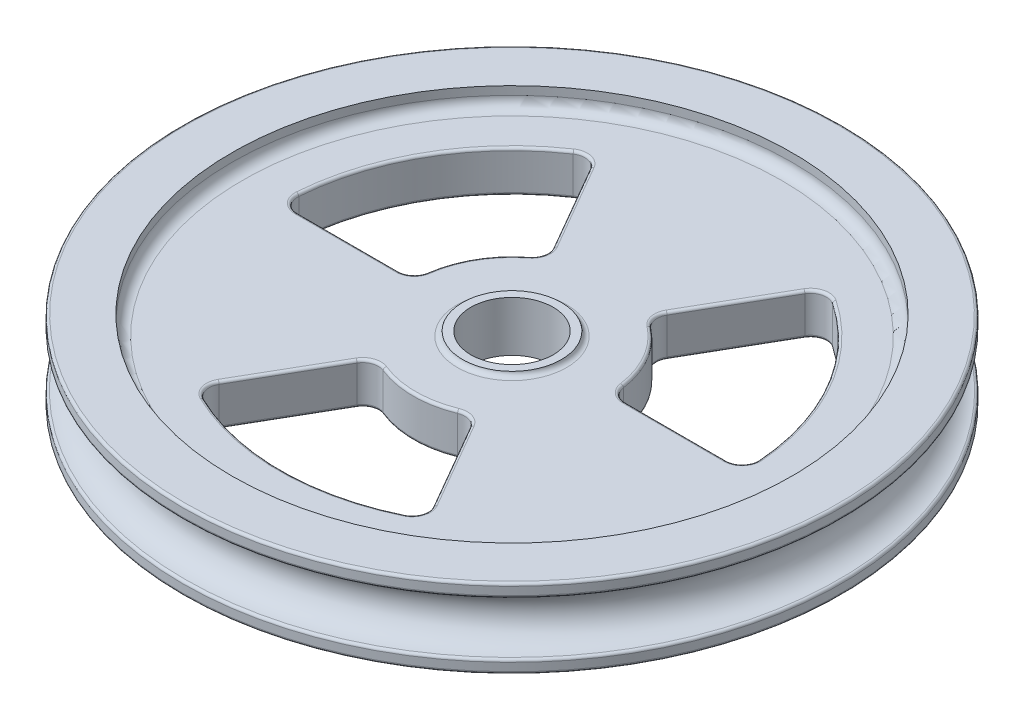
SolidWorks part; units mm, degrees
ref_plane "Front Plane" through (0, 0, 0) normal (0, 0, 1) x (1, 0, 0)
ref_plane "Top Plane" through (0, 0, 0) normal (0, 1, 0) x (1, 0, 0)
ref_plane "Right Plane" through (0, 0, 0) normal (1, 0, 0) x (0, 0, -1)
sketch "Sketch1" plane through (0, 0, 0) normal (0, 0, 1) x (1, 0, 0)
  line L0 (100, 12) -> (0, 12)
  line L1 (0, 12) -> (0, -12)
  line L2 (0, -12) -> (100, -12)
  line L3 (100, -12) -> (100, -8)
  line L4 (100, 8) -> (100, 12)
  line L5 (0, 12) -> (0, -12) construction
  arc A0 (100, -8) -> (100, 8) centre (100, 0) cw
  dimension "D1" = 100
revolve "Revolve1" add sketch "Sketch1" angle 360 about L5 reverse direction yes
hole_wizard "Hole1" positions "Sketch3" profile "Sketch2" legacy
sketch "Sketch3" plane through (0, -12, 0) normal (0, -1, 0) x (-1, 0, 0)
  point P0 (0, 0)
sketch "Sketch2" plane through (0, -12, 0) normal (1, 0, 0) x (0, 0, -1)
  line L0 (0, 0) -> (0, 5.715)
  line L1 (0, 5.715) -> (85, 5.715)
  line L2 (85, 5.715) -> (85, 0)
  line L3 (85, 0) -> (0, 0)
  line L4 (0, 110) -> (0, -10) construction
  dimension "Diameter" = 170
  dimension "Depth" = 5.715
hole_wizard "Hole2" positions "Sketch5" profile "Sketch4" legacy
sketch "Sketch5" plane through (0, 12, 0) normal (0, 1, 0) x (1, 0, 0)
  point P0 (0, 0)
sketch "Sketch4" plane through (0, 12, 0) normal (1, 0, 0) x (0, 0, 1)
  line L0 (0, 0) -> (0, 5.715)
  line L1 (0, 5.715) -> (85, 5.715)
  line L2 (85, 5.715) -> (85, 0)
  line L3 (85, 0) -> (0, 0)
  line L4 (0, 110) -> (0, -10) construction
  dimension "Diameter" = 170
  dimension "Depth" = 5.715
sketch "Sketch6" plane through (0, -6.285, 0) normal (0, -1, 0) x (1, 0, 0)
  line L0 (-35, -60.6218) -> (-15, -25.9808)
  line L1 (-30, 0) -> (-70, 0)
  arc A0 (-70, 0) -> (-35, -60.6218) centre (0, 0) ccw
  arc A1 (-15, -25.9808) -> (-30, 0) centre (0, 0) cw
  point P5 (0, 0)
  dimension "D3" = 70
  dimension "D1" = 30
extrude "Cut-Extrude1" cut sketch "Sketch6" against normal through all
sketch "Sketch7" plane through (0, -6.285, 0) normal (0, -1, 0) x (1, 0, 0)
  line L0 (-35, 60.6218) -> (-15, 25.9808)
  line L1 (15, 25.9808) -> (35, 60.6218)
  arc A0 (35, 60.6218) -> (-35, 60.6218) centre (0, 0) ccw
  arc A1 (-15, 25.9808) -> (15, 25.9808) centre (0, 0) cw
  point P5 (0, 0)
  dimension "D1" = 30
  dimension "D2" = 70
extrude "Cut-Extrude2" cut sketch "Sketch7" against normal through all
sketch "Sketch8" plane through (0, 6.285, 0) normal (0, 1, 0) x (-1, 0, 0)
  line L0 (-35, -60.6218) -> (-15, -25.9808)
  line L1 (-30, 0) -> (-70, 0)
  arc A0 (-15, -25.9808) -> (-30, 0) centre (0, 0) cw
  arc A1 (-70, 0) -> (-35, -60.6218) centre (0, 0) ccw
  point P5 (0, 0)
  dimension "D1" = 30
  dimension "D2" = 70
extrude "Cut-Extrude3" cut sketch "Sketch8" against normal through all
sketch "Sketch9" plane through (0, 0, 0) normal (0, 0, 1) x (1, 0, 0)
  line L0 (15, 7.62) -> (0, 7.62)
  line L1 (0, 7.62) -> (0, 1.905)
  line L2 (0, 1.905) -> (15, 1.905)
  line L3 (15, 1.905) -> (15, 7.62)
  line L4 (0, 7.62) -> (0, 1.905) construction
  dimension "D1" = 15
revolve "Revolve2" add sketch "Sketch9" angle 360 about L4 reverse direction yes
ref_plane "Plane1" through (0, 0, 0) normal (0, 0, -1) x (-1, 0, 0)
sketch "Sketch10" plane through (0, 0, 0) normal (0, 0, -1) x (-1, 0, 0)
  line L0 (-15, -7.62) -> (0, -7.62)
  line L1 (0, -7.62) -> (0, -1.0806)
  line L2 (0, -1.0806) -> (-15, -1.0806)
  line L3 (-15, -1.0806) -> (-15, -7.62)
  line L4 (0, -7.62) -> (0, -1.0806) construction
  point P5 (0, -1.0806)
  dimension "D1" = 15
revolve "Revolve3" add sketch "Sketch10" angle 360 about L4 reverse direction yes
hole_wizard "M18 Clearance Hole1" positions "Sketch12" profile "Sketch11" hole size "M18" standard "ANSI Metric"
sketch "Sketch12" plane through (0, -7.62, 0) normal (0, -1, 0) x (-1, 0, 0)
  point P0 (0, 0)
  point P1 (0, 0)
  point P2 (1.6309, 0)
  point P3 (0, 0)
  point P6 (0, 0)
  point P7 (0, 0)
  point P8 (0, 0)
  point P9 (0, 0)
sketch "Sketch11" plane through (0, -7.62, 0) normal (1, 0, 0) x (0, 0, -1)
  line L0 (0, 0) -> (0, 27.1308)
  line L1 (0, 27.1308) -> (12.5, 19.62)
  line L2 (12.5, 19.62) -> (12.5, 0)
  line L5 (12.5, 0) -> (0, 0)
  line L10 (0, 27.1308) -> (-12.5, 19.62) construction
  line L11 (0, -6.35) -> (0, 107.95) construction
  dimension "Hole Dia." = 25
  dimension "Hole Depth" = 19.62
  dimension "Drill Angle" = 118
fillet "Fillet1" radius 4.7625 12 edges at (-35, 0, -60.6218) (-35, 0, 60.6218) (15, 0, 25.9808) (15, 0, -25.9808) (-70, 0, 0) (35, 0, -60.6218) (-15, 0, 25.9808) (70, 0, 0) (35, 0, 60.6218) (-15, 0, -25.9808) (-30, 0, 0) (30, 0, 0) tangent propagation no
fillet "Fillet2" radius 0.7938 52 edges at (-35.5924, 6.285, -58.6075) (-60.6218, 6.285, -35) (-24.8745, 6.285, -43.084) (-68.5518, 6.285, -1.5202) (-16.6678, 6.285, -26.5262) (-49.7491, 6.285, 0) (-25.9808, 6.285, -15) (-31.3063, 6.285, -1.1716) (68.5518, -6.285, -1.5202) (60.6218, -6.285, -35) (49.7491, -6.285, 0) (35.5924, -6.285, -58.6075) (31.3063, -6.285, -1.1716) (24.8745, -6.285, -43.084) (25.9808, -6.285, -15) (16.6678, -6.285, -26.5262) (-32.9594, 6.285, 60.1277) (0, 6.285, 70) (-24.8745, 6.285, 43.084) (32.9594, 6.285, 60.1277) (-14.6385, 6.285, 27.6979) (24.8745, 6.285, 43.084) (0, 6.285, 30) (14.6385, 6.285, 27.6979) (16.6678, 6.285, -26.5262) (24.8745, 6.285, -43.084) (25.9808, 6.285, -15) (35.5924, 6.285, -58.6075) (31.3063, 6.285, -1.1716) (60.6218, 6.285, -35) (49.7491, 6.285, 0) (68.5518, 6.285, -1.5202) (-35.5924, -6.285, -58.6075) (-60.6218, -6.285, -35) (-24.8745, -6.285, -43.084) (-68.5518, -6.285, -1.5202) (-16.6678, -6.285, -26.5262) (-49.7491, -6.285, 0) (-25.9808, -6.285, -15) (-31.3063, -6.285, -1.1716) (-32.9594, -6.285, 60.1277) (0, -6.285, 70) (-24.8745, -6.285, 43.084) (32.9594, -6.285, 60.1277) (-14.6385, -6.285, 27.6979) (24.8745, -6.285, 43.084) (0, -6.285, 30) (14.6385, -6.285, 27.6979) (0, 8, -100) (0, 12, -100) (0, -12, -100) (0, -8, -100) tangent propagation no
fillet "Fillet3" radius 1.5875 2 edges at (0, 6.285, -15) (0, -6.285, 15) tangent propagation no
fillet "Fillet4" radius 3.175 2 edges at (0, 6.285, 85) (0, -6.285, -85) tangent propagation no
